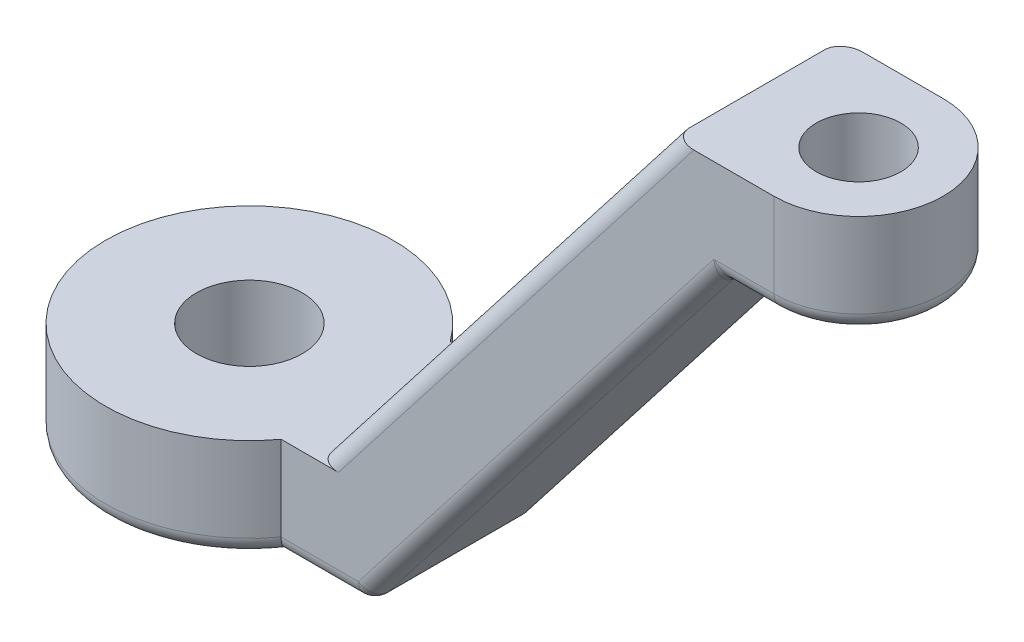
SolidWorks part; units mm, degrees
ref_plane "Front Plane" through (0, 0, 0) normal (0, 0, 1) x (1, 0, 0)
ref_plane "Top Plane" through (0, 0, 0) normal (0, 1, 0) x (1, 0, 0)
ref_plane "Right Plane" through (0, 0, 0) normal (1, 0, 0) x (0, 0, -1)
sketch "Sketch2" plane through (0, 0, 0) normal (0, 0, 1) x (1, 0, 0)
  line L0 (-11.43, 0) -> (0, 0)
  line L1 (0, 0) -> (26.67, 34.29)
  line L2 (26.67, 34.29) -> (34.29, 34.29)
  line L3 (-11.43, -7.62) -> (3.7268, -7.62)
  line L4 (3.7268, -7.62) -> (30.3968, 26.67)
  line L5 (30.3968, 26.67) -> (34.29, 26.67)
  line L6 (-11.43, 0) -> (-11.43, -7.62)
  line L7 (34.29, 34.29) -> (34.29, 26.67)
  dimension "D1" = 45.72
  dimension "D2" = 7.62
  dimension "D3" = 11.43
  dimension "D4" = 34.29
  dimension "D5" = 7.62
extrude "Boss-Extrude2" add sketch "Sketch2" along normal blind 12.7
sketch "Sketch3" plane through (0, 0, 0) normal (0, 1, 0) x (1, 0, 0)
  line L0 (-11.43, -12.7) -> (-11.43, 0) construction
  circle A0 centre (-11.43, -6.35) radius 10.795
  point P6 (-11.43, -6.35)
  dimension "D1" = 21.59
extrude "Boss-Extrude3" add sketch "Sketch3" against normal up to surface (7.62 mm away) up to face at (-3.8516, -7.62, 6.35)
sketch "Sketch4" plane through (0, 34.29, 0) normal (0, 1, 0) x (1, 0, 0)
  line L0 (34.29, -12.7) -> (26.67, -12.7) construction
  line L1 (34.29, -12.7) -> (34.29, 0) construction
  line L2 (34.29, 0) -> (34.29, -12.7)
  arc A0 (34.29, 0) -> (34.29, -12.7) centre (34.29, -6.35) cw
extrude "Boss-Extrude4" add sketch "Sketch4" against normal up to surface (7.62 mm away) up to face at (32.3434, 26.67, 6.35)
sketch "Sketch5" plane through (0, 0, 0) normal (0, 1, 0) x (1, 0, 0)
  circle A0 centre (-11.43, -6.35) radius 3.9688
  circle A1 centre (34.29, -6.35) radius 3.175
  arc A2 (34.29, -12.7) -> (34.29, 0) centre (34.29, -6.35) ccw construction
  arc A3 (-2.7002, 0) -> (-2.7002, -12.7) centre (-11.43, -6.35) ccw construction
  dimension "D1" = 6.35
  dimension "D2" = 7.9375
extrude "Cut-Extrude1" cut sketch "Sketch5" against normal through all both and the other way through all
fillet "Fillet1" radius 1.27 4 edges at (17.0618, 9.525, 0) (17.0618, 9.525, 12.7) (13.335, 17.145, 0) (13.335, 17.145, 12.7)
fillet "Fillet2" radius 1.27 9 edges at (31.539, 26.67, 0) (31.539, 26.67, 12.7) (40.64, 26.67, 6.35) (-22.225, -7.62, 6.35) (-0.2911, -7.62, 12.7) (3.2556, -7.62, 12.328) (-0.2911, -7.62, 0) (3.2556, -7.62, 0.372) (3.7268, -7.62, 6.35)
fillet "Fillet3" radius 1.27 3 edges at (30.2149, 27.042, 0.372) (30.2149, 27.042, 12.328) (30.3968, 26.67, 6.35)
